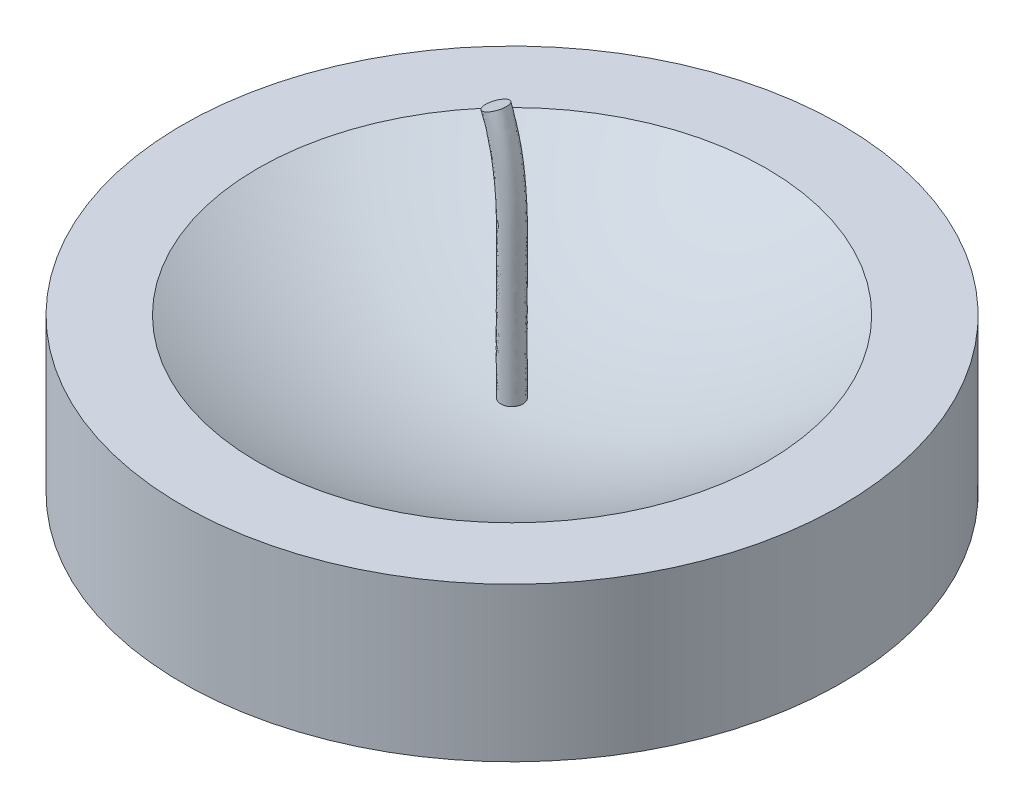
SolidWorks part; units mm, degrees
ref_plane "Front Plane" through (0, 0, 0) normal (0, 0, 1) x (1, 0, 0)
ref_plane "Top Plane" through (0, 0, 0) normal (0, 1, 0) x (1, 0, 0)
ref_plane "Right Plane" through (0, 0, 0) normal (1, 0, 0) x (0, 0, -1)
sketch "Sketch1" plane through (0, 0, 0) normal (0, 0, 1) x (1, 0, 0)
  line L1 (0, 0) -> (19.05, 0)
  line L2 (0, 0) -> (0, 8.89)
  line L3 (0, 8.89) -> (19.05, 8.89)
  line L4 (19.05, 0) -> (19.05, 8.89)
  dimension "D1" = 19.05
  dimension "D2" = 8.89
revolve "Revolve1" add sketch "Sketch1" angle 360 about L2
sketch "Sketch15" plane through (0, 0, 0) normal (0, 0, 1) x (1, 0, 0)
  line L0 (0, 8.89) -> (0, 4.745)
  line L1 (19.05, 8.89) -> (-19.05, 8.89) construction
  line L2 (0, 8.89) -> (14.699, 8.89)
  line L3 (2.1422, 4.745) -> (-2.1422, 4.745) construction
  spline S0 degree 3 poles (0, 4.745) (5.2643, 4.745) (10.162, 6.3297) (14.699, 8.89) knots 0 0 0 0 1 1 1 1
revolve "Cut-Revolve4" cut sketch "Sketch15" angle 360 about L0
sketch "Sketch16" plane through (0, 0, 0) normal (0, 0, 1) x (1, 0, 0)
  line L0 (-19.05, 0) -> (19.05, 0) construction
  line L1 (0, 3.3826) -> (0, -3.414) construction
  line L2 (0, 14.1193) -> (0, 9.0915) construction
  spline S0 degree 3 poles (0, 0) (0, 3.823) (-0.0603, 10.1273) (0.0612, 16.4089) (-0.9359, 18.9161) knots 0 0 0 0 0.597052 1 1 1 1
  point P2 (-0.9359, 18.9161)
sweep "Sweep2" add path "Sketch16" circular profile diameter 1.27 parameters "D3"=1.27
